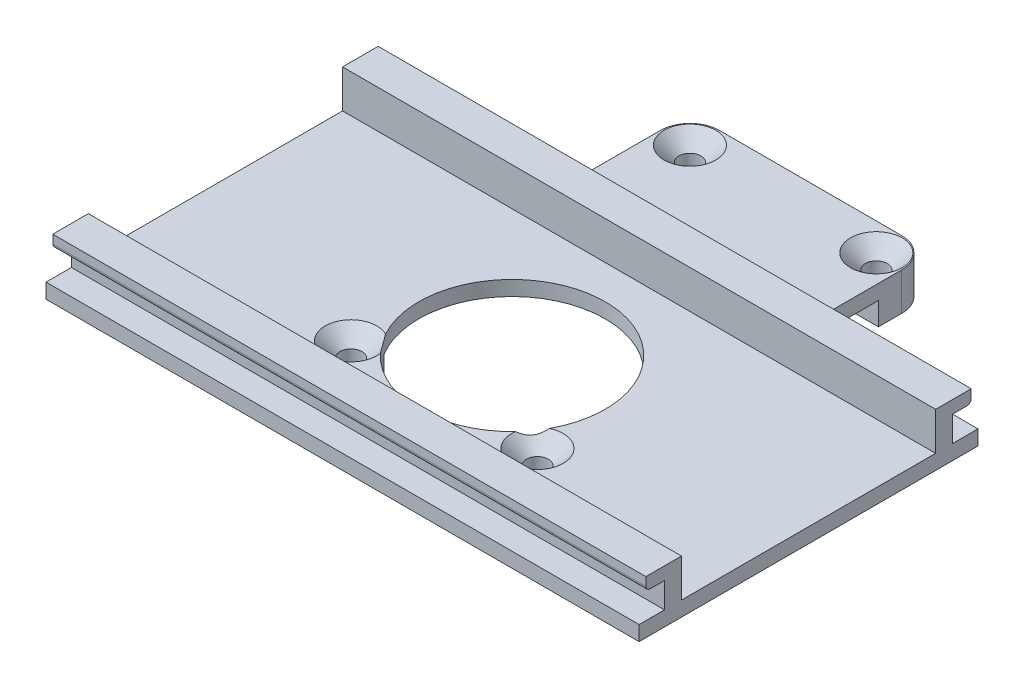
SolidWorks part; units mm, degrees
ref_plane "Front Plane" through (0, 0, 0) normal (0, 0, 1) x (1, 0, 0)
ref_plane "Top Plane" through (0, 0, 0) normal (0, 1, 0) x (1, 0, 0)
ref_plane "Right Plane" through (0, 0, 0) normal (1, 0, 0) x (0, 0, -1)
sketch "Sketch1" plane through (0, 0, 0) normal (0, 1, 0) x (1, 0, 0)
  line L2 (35, 20) -> (35, -20)
  line L3 (35, -20) -> (-35, -20)
  line L4 (-35, 20) -> (-35, -20)
  line L5 (35, 20) -> (-35, -20) construction
  line L6 (35, -20) -> (-35, 20) construction
  line L12 (0, 35.25) -> (-14.25, 35.25)
  line L13 (0, 35.25) -> (14.25, 35.25)
  line L14 (14.25, 35.25) -> (14.25, 20)
  line L15 (14.25, 20) -> (35, 20)
  line L16 (-14.25, 35.25) -> (-14.25, 20)
  line L17 (-14.25, 20) -> (-35, 20)
  point P0 (0, 0)
  point P7 (0, 0)
  dimension "D1" = 40
  dimension "D2" = 70
  dimension "D4" = 28.5
extrude "Boss-Extrude1" add sketch "Sketch1" along normal blind 1.75
sketch "Sketch2" plane through (0, 1.75, 0) normal (0, 1, 0) x (1, 0, 0)
  line L1 (35, 15) -> (-35, 15)
  line L3 (35, 17) -> (-35, 17)
  line L4 (-35, 17) -> (-35, 15)
  line L5 (35, 17) -> (35, 15)
  line L7 (-35, -15) -> (35, -15)
  line L9 (-35, -17) -> (35, -17)
  line L10 (-35, -15) -> (-35, -17)
  line L11 (35, -15) -> (35, -17)
  dimension "D2" = 2
  dimension "D4" = 2
extrude "Boss-Extrude2" add sketch "Sketch2" along normal blind 3
sketch "Sketch3" plane through (0, 4.75, 0) normal (0, 1, 0) x (1, 0, 0)
  line L8 (-35, 15) -> (35, 15)
  line L9 (35, 15) -> (35, 17) construction
  line L10 (-35, 15) -> (35, 15) construction
  line L12 (-35, -15) -> (35, -15)
  line L25 (-35, 15) -> (-35, 19.2)
  line L26 (-35, 19.2) -> (35, 19.2)
  line L28 (35, 19.2) -> (35, 15)
  line L29 (-35, -15) -> (-35, -19.2)
  line L30 (-35, -19.2) -> (35, -19.2)
  line L32 (35, -19.2) -> (35, -15)
extrude "Boss-Extrude3" add sketch "Sketch3" along normal blind 1.5
sketch "Sketch4" plane through (0, 0, 0) normal (0, -1, 0) x (1, 0, 0)
  line L0 (-11, -35.25) -> (-8, -35.25)
  line L37 (14.25, -35.25) -> (-14.25, -35.25) construction
  line L39 (8, -29) -> (14.25, -29)
  line L41 (14.25, -20) -> (14.25, -35.25) construction
  line L51 (14.25, -29) -> (14.25, -35.25)
  line L52 (14.25, -35.25) -> (8, -35.25)
  line L53 (8, -35.25) -> (8, -29)
  line L54 (14.25, 8) -> (14.25, 5)
  line L55 (-11, -35.25) -> (-14.25, -35.25)
  line L56 (-14.25, -35.25) -> (-14.25, -32)
  line L57 (-14.25, -35.25) -> (-14.25, -20) construction
  line L58 (-14.25, -32) -> (-14.25, -29)
  line L59 (-14.25, -29) -> (-11, -29)
  line L62 (-11, -29) -> (-8, -29)
  line L63 (-8, -29) -> (-8, -32)
  line L64 (-8, -32) -> (-8, -35.25)
  line L65 (-14.25, 11.25) -> (-8, 11.25)
  line L66 (-14.25, 8) -> (-14.25, 5)
  line L67 (-14.25, 5) -> (-11, 5)
  line L68 (14.25, 11.25) -> (14.25, 8)
  line L72 (-11, 5) -> (-8, 5)
  line L74 (8, 8.25) -> (8, 11.25)
  line L77 (-14.25, 8) -> (-14.25, 11.25)
  line L84 (-8, 5) -> (-8, 8.25)
  line L85 (14.25, 5) -> (8, 5)
  line L87 (-8, 11.25) -> (-8, 8.25)
  line L88 (8, 5) -> (8, 8.25)
  line L89 (8, 11.25) -> (14.25, 11.25)
extrude "Boss-Extrude4" add sketch "Sketch4" along normal blind 2.7
sketch "Sketch6" plane through (0, -2.7, 0) normal (0, -1, 0) x (1, 0, 0)
  circle A6 centre (-11, -32) radius 1.3
  circle A7 centre (11, -32) radius 1.3
  circle A8 centre (-11, 8) radius 1.3
  circle A9 centre (11, 8) radius 1.3
extrude "Cut-Extrude2" cut sketch "Sketch6" against normal through all
fillet "Fillet3" radius 3.5 8 edges at (14.25, -0.475, -35.25) (-14.25, -0.475, -35.25) (-8, -1.35, -29) (8, -1.35, -29) (8, -1.35, 5) (-8, -1.35, 5) (14.25, -1.35, 11.25) (-14.25, -1.35, 11.25)
sketch "Sketch7" plane through (0, 1.75, 0) normal (0, 1, 0) x (1, 0, 0)
  circle A0 centre (0, 0) radius 11
extrude "Cut-Extrude3" cut sketch "Sketch7" against normal through all contours A0
chamfer "Chamfer1" distance 1.75 angle 45 4 edges at (11, 1.75, -33.3) (-11, 1.75, -33.3) (-11, 1.75, 6.7) (11, 1.75, 6.7)
fillet "Fillet4" radius 0.5 2 edges at (0, 4.75, 19.2) (0, 4.75, -19.2)
